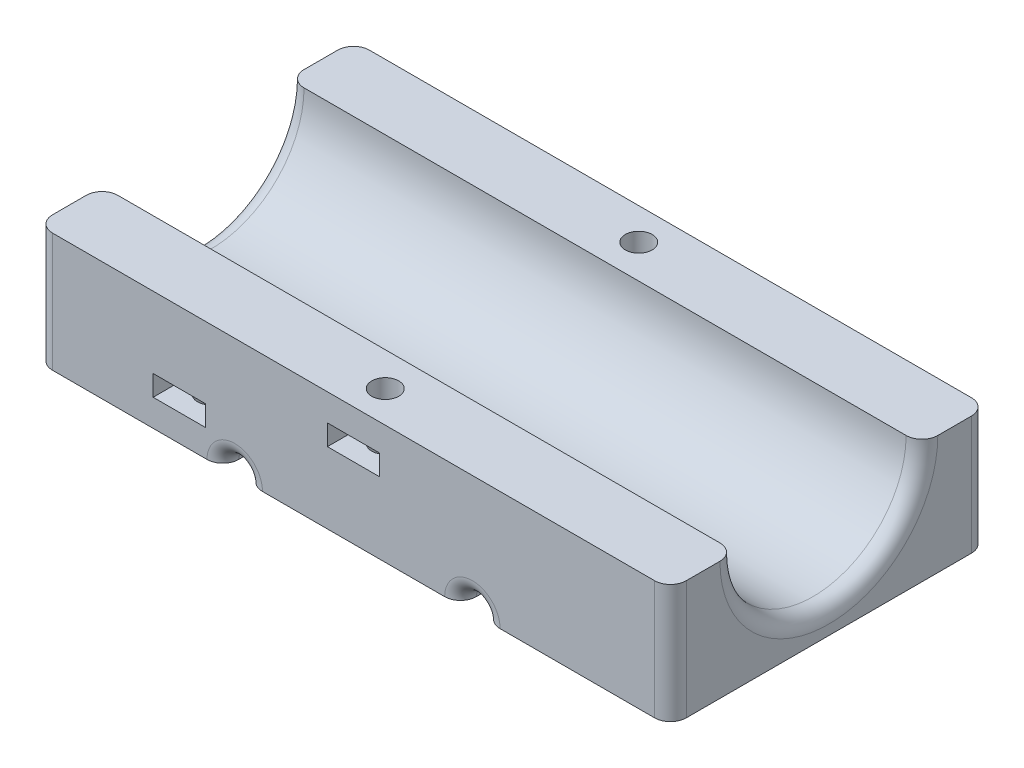
SolidWorks part; units mm, degrees
ref_plane "Front Plane" through (0, 0, 0) normal (0, 0, 1) x (1, 0, 0)
ref_plane "Top Plane" through (0, 0, 0) normal (0, 1, 0) x (1, 0, 0)
ref_plane "Right Plane" through (0, 0, 0) normal (1, 0, 0) x (0, 0, -1)
sketch "Sketch3" plane through (0, 0, 0) normal (1, 0, 0) x (0, 0, -1)
  line L0 (40.3225, 19.05) -> (50.8, 19.05)
  line L1 (0, 0) -> (50.8, 0)
  line L2 (0, 0) -> (0, 19.05)
  line L3 (0, 19.05) -> (10.4775, 19.05)
  line L4 (50.8, 0) -> (50.8, 19.05)
  arc A0 (10.4775, 19.05) -> (40.3225, 19.05) centre (25.4, 19.05) ccw
  point P9 (25.4, 0)
  dimension "D1" = 14.9225
  dimension "D2" = 50.8
  dimension "D3" = 19.05
extrude "Boss-Extrude2" add sketch "Sketch3" along normal blind 101.6
sketch "Sketch4" plane through (0, 0, 0) normal (0, 0, 1) x (1, 0, 0)
  line L0 (101.6, 0) -> (0, 0) construction
  line L2 (31.75, 0) -> (69.85, 0) construction
  circle A0 centre (31.75, 0) radius 1.905
  circle A1 centre (69.85, 0) radius 1.905
  point P6 (41.5832, 0)
  point P7 (61.3742, 0)
  point P8 (50.8, 0)
  point P9 (50.8, 0)
  dimension "D1" = 3.81
  dimension "D2" = 38.1
extrude "Cut-Extrude1" cut sketch "Sketch4" against normal through all
hole_wizard "#6 Clearance Hole1" positions "Sketch5" profile "Sketch6" hole size "#6" standard "ANSI Inch"
sketch "Sketch5" plane through (0, 19.05, 0) normal (0, 1, 0) x (1, 0, 0)
  line L0 (101.6, 0) -> (0, 0) construction
  line L1 (0, 25.4) -> (101.6, 25.4) construction
  line L2 (0, 40.3225) -> (0, 10.4775) construction
  line L3 (101.6, 10.4775) -> (101.6, 40.3225) construction
  line L4 (50.8, 0) -> (50.8, 50.8) construction
  line L5 (101.6, 50.8) -> (0, 50.8) construction
  point P0 (50.8, 5.08)
  point P2 (50.8, 45.72)
  dimension "D1" = 5.08
sketch "Sketch6" plane through (50.8, 19.05, -5.08) normal (1, 0, 0) x (0, 0, 1)
  line L0 (0, 0) -> (0, 13.9934)
  line L1 (0, 13.9934) -> (2.1526, 12.7)
  line L2 (2.1526, 12.7) -> (2.1526, 0)
  line L5 (2.1526, 0) -> (0, 0)
  line L10 (0, 13.9934) -> (-2.1527, 12.7) construction
  line L11 (0, -6.35) -> (0, 107.95) construction
  dimension "Hole Dia." = 4.3053
  dimension "Hole Depth" = 12.7
  dimension "Drill Angle" = 118
ref_plane "Plane1" through (0, 11.43, 0) normal (0, 1, 0) x (1, 0, 0)
sketch "Sketch8" plane through (0, 11.43, 0) normal (0, 1, 0) x (1, 0, 0)
  line L0 (101.6, 0) -> (0, 0) construction
  line L1 (46.609, 9.144) -> (54.991, 9.144)
  line L2 (46.609, 9.144) -> (46.609, 0)
  line L3 (46.609, 0) -> (54.991, 0)
  line L4 (54.991, 9.144) -> (54.991, 0)
  line L5 (101.6, 50.8) -> (0, 50.8) construction
  line L6 (46.609, 41.656) -> (54.991, 41.656)
  line L7 (46.609, 41.656) -> (46.609, 50.8)
  line L8 (46.609, 50.8) -> (54.991, 50.8)
  line L9 (54.991, 41.656) -> (54.991, 50.8)
  point P12 (50.8, 9.144)
  dimension "D1" = 8.382
  dimension "D2" = 4.064
extrude "Cut-Extrude2" cut sketch "Sketch8" along normal blind 3.302
hole_wizard "#6 Clearance Hole2" positions "Sketch9" profile "Sketch10" hole size "#6" standard "ANSI Inch"
sketch "Sketch9" plane through (0, 0, 0) normal (0, -1, 0) x (-1, 0, 0)
  line L0 (-101.6, 0) -> (-101.6, 50.8) construction
  line L1 (-101.6, 50.8) -> (-71.755, 50.8) construction
  line L4 (-78.74, 45.72) -> (-22.86, 5.08) construction
  line L5 (-29.845, 0) -> (0, 0) construction
  point P0 (-78.74, 45.72)
  point P2 (-22.86, 5.08)
  point P30 (-50.8, 25.4)
  dimension "D1" = 55.88
  dimension "D2" = 5.08
  dimension "D3" = 50.8
  dimension "D4" = 5.08
sketch "Sketch10" plane through (78.74, 0, -45.72) normal (1, 0, 0) x (0, 0, -1)
  line L0 (0, 0) -> (0, 13.9934)
  line L1 (0, 13.9934) -> (2.1526, 12.7)
  line L2 (2.1526, 12.7) -> (2.1526, 0)
  line L5 (2.1526, 0) -> (0, 0)
  line L10 (0, 13.9934) -> (-2.1527, 12.7) construction
  line L11 (0, -6.35) -> (0, 107.95) construction
  dimension "Hole Dia." = 4.3053
  dimension "Hole Depth" = 12.7
  dimension "Drill Angle" = 118
ref_plane "Plane2" through (0, 7.62, 0) normal (0, -1, 0) x (-1, 0, 0)
sketch "Sketch11" plane through (0, 7.62, 0) normal (0, -1, 0) x (-1, 0, 0)
  line L0 (-101.6, 50.8) -> (-71.755, 50.8) construction
  line L1 (-82.931, 41.656) -> (-74.549, 41.656)
  line L2 (-82.931, 41.656) -> (-82.931, 50.8)
  line L3 (-82.931, 50.8) -> (-74.549, 50.8)
  line L4 (-74.549, 41.656) -> (-74.549, 50.8)
  line L10 (-67.945, 0) -> (-33.655, 0) construction
  line L11 (-27.051, 0) -> (-18.669, 0)
  line L12 (-27.051, 0) -> (-27.051, 9.144)
  line L13 (-27.051, 9.144) -> (-18.669, 9.144)
  line L14 (-18.669, 0) -> (-18.669, 9.144)
  point P24 (-78.74, 41.656)
  point P25 (-22.86, 9.144)
  dimension "D1" = 8.382
  dimension "D2" = 4.064
extrude "Cut-Extrude3" cut sketch "Sketch11" along normal blind 3.302
fillet "Fillet1" radius 2.54 10 edges at (101.6, 4.1275, -25.4) (0, 4.1275, -25.4) (0, 9.525, -50.8) (101.6, 9.525, -50.8) (0, 9.525, 0) (101.6, 9.525, 0) (69.85, 1.905, -50.8) (69.85, 1.905, 0) (31.75, 1.905, -50.8) (31.75, 1.905, 0)
